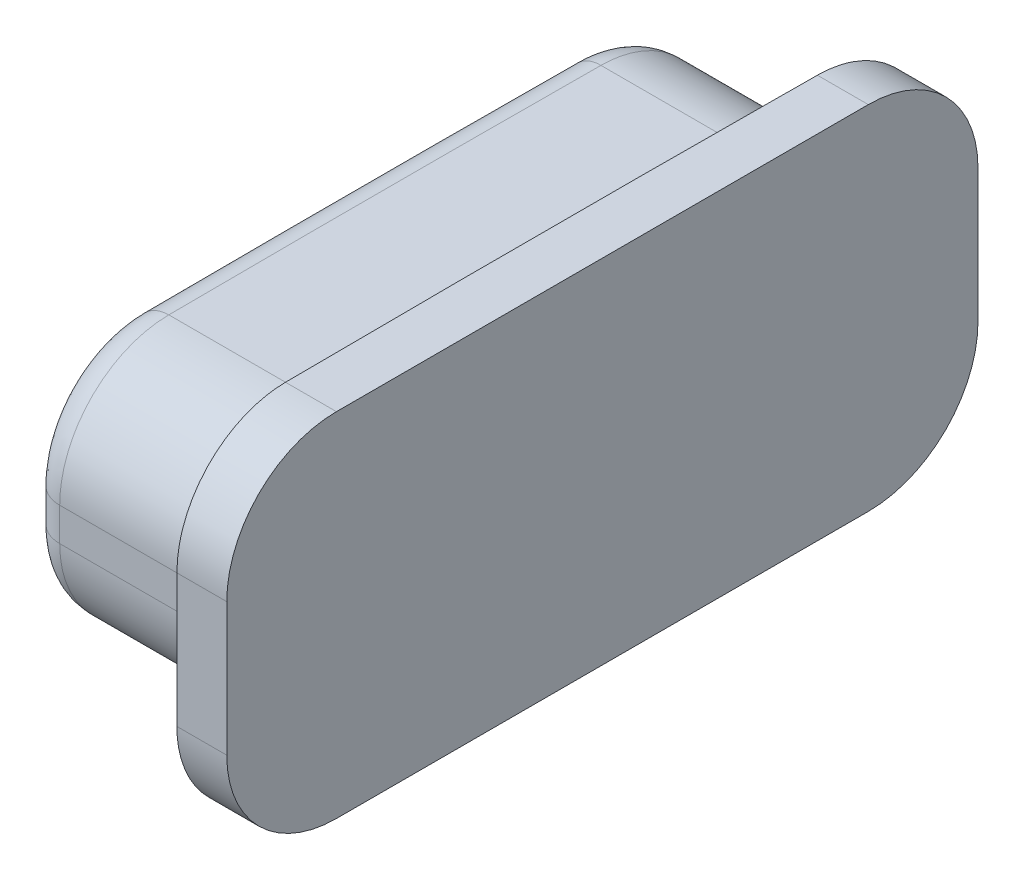
SolidWorks part; units mm, degrees
ref_plane "Front Plane" through (0, 0, 0) normal (0, 0, 1) x (1, 0, 0)
ref_plane "Top Plane" through (0, 0, 0) normal (0, 1, 0) x (1, 0, 0)
ref_plane "Right Plane" through (0, 0, 0) normal (1, 0, 0) x (0, 0, -1)
sketch "Sketch1" plane through (0, 0, 0) normal (0, 1, 0) x (1, 0, 0)
  line L0 (0, 0) -> (-20.8, 0) construction
  line L1 (0, 0) -> (780.6598, 0) construction
  line L2 (-19.8, 21.6348) -> (-19.8, -21.6348) construction
  line L3 (-20.776, 4.9) -> (-17.7759, 4.9)
  line L4 (-17.7679, 5.65) -> (-17.0179, 5.65)
  line L5 (-20.776, -4.9) -> (-17.7759, -4.9)
  line L6 (-17.7679, -5.65) -> (-17.0179, -5.65)
  line L7 (-17.0179, 5.65) -> (-17.0179, -5.65)
  circle A1 centre (480.2, 0) radius 500 construction
  arc A2 (-17.7679, 5.65) -> (-17.7759, 4.9) centre (480.2, 0) ccw
  arc A3 (-20.776, 4.9) -> (-20.776, -4.9) centre (480.2, 0) ccw
  arc A5 (-17.7759, -4.9) -> (-17.7679, -5.65) centre (480.2, 0) ccw
  point P7 (-19.8, 0)
  dimension "D2" = 1000
  dimension "D3" = 996
  dimension "D4" = 1002
  dimension "D1" = 19.8
  dimension "D6" = 4.9
  dimension "D7" = 0.75
extrude "Boss-Extrude1" add sketch "Sketch1" along normal mid plane 5.3
sketch "Sketch2" plane through (0, 2.65, 0) normal (0, 1, 0) x (1, 0, 0)
  line L0 (-39.3064, 0) -> (601.6204, 0) construction
  line L1 (-17.7759, 4.9) -> (-20.776, 4.9)
  line L2 (-17.7759, -4.9) -> (-20.776, -4.9)
  arc A0 (-17.7759, 4.9) -> (-17.7759, -4.9) centre (480.2, 0) ccw
  arc A2 (-20.776, 4.9) -> (-20.776, -4.9) centre (480.2, 0) ccw
  point P4 (-32.7807, 0.1571)
  dimension "D2" = 501
extrude "Cut-Extrude2" cut sketch "Sketch2" against normal blind 0.75
mirror "Mirror1" about plane through (0, 0, 0) normal (0, 1, 0) of "Cut-Extrude2"
fillet "Fillet3" radius 1.65 8 edges at (-17.3929, -2.65, 5.65) (-19.276, -1.9, 4.9) (-17.3929, 2.65, 5.65) (-19.276, 1.9, 4.9) (-17.3929, 2.65, -5.65) (-19.276, 1.9, -4.9) (-17.3929, -2.65, -5.65) (-19.276, -1.9, -4.9)
fillet "Fillet4" radius 0.5 8 edges at (-20.7794, -1.2807, -4.5385) (-20.776, 0, -4.9) (-20.7817, 1.5384, -4.2808) (-20.8, 1.9, 0) (-20.7794, 1.2807, 4.5385) (-20.776, 0, 4.9) (-20.7817, -1.5384, 4.2808) (-20.8, -1.9, 0)
